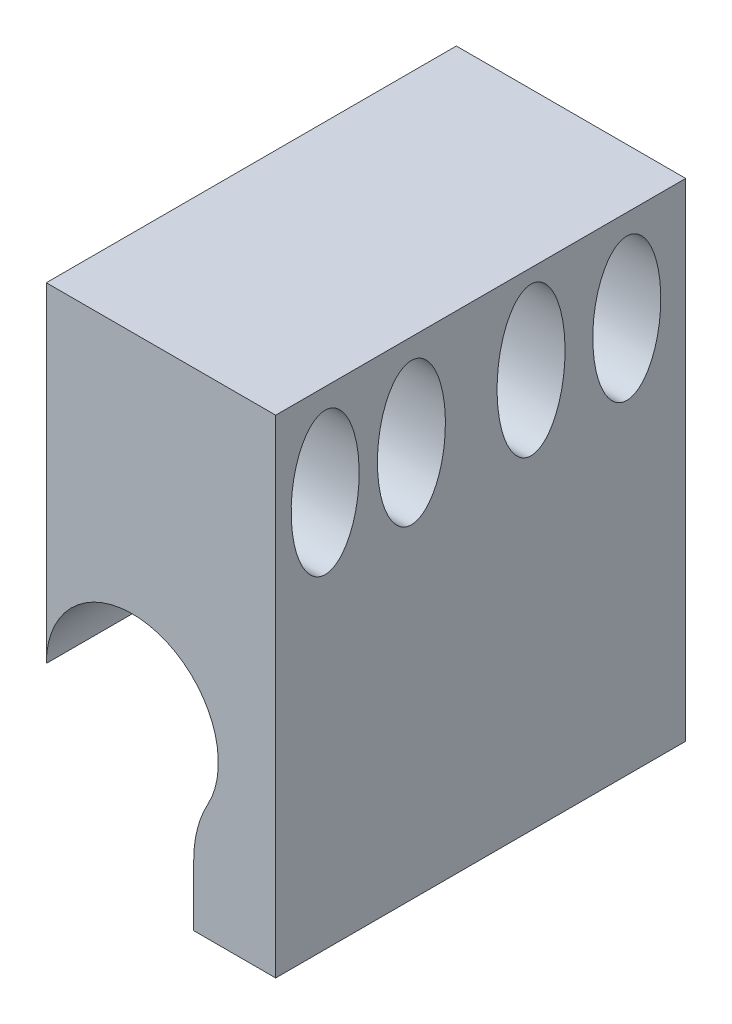
SolidWorks part; units mm, degrees
ref_plane "前视基准面" through (0, 0, 0) normal (0, 0, 1) x (1, 0, 0)
ref_plane "上视基准面" through (0, 0, 0) normal (0, 1, 0) x (1, 0, 0)
ref_plane "右视基准面" through (0, 0, 0) normal (1, 0, 0) x (0, 0, -1)
sketch "草图1" plane through (0, 0, 0) normal (0, 0, 1) x (1, 0, 0)
  line L1 (0, 0) -> (16, 0)
  line L2 (0, 0) -> (0, -34)
  line L3 (0, -34) -> (16, -34)
  line L4 (16, 0) -> (16, -34)
  dimension "D1" = 16
  dimension "D2" = 34
extrude "凸台-拉伸1" add sketch "草图1" along normal blind 28.6
sketch "草图2" plane through (0, 0, 28.6) normal (0, 0, 1) x (1, 0, 0)
  line L0 (0, 0) -> (12, 0) construction
  line L1 (16, 0) -> (0, 0) construction
  line L2 (12, 0) -> (12, -23) construction
  line L3 (12, -23) -> (6, -23) construction
  line L4 (9.3178, -34) -> (10.2842, -34)
  line L5 (0, -34) -> (16, -34) construction
  line L6 (10.2842, -34) -> (10.2842, -29.7156)
  line L7 (10.2842, -27.2007) -> (10.2842, -34)
  line L8 (0, -34) -> (0.0151, -23.4251)
  line L9 (10.2842, -34) -> (0, -34)
  arc A0 (11.2646, -25.8781) -> (0.0151, -23.4251) centre (6, -23) ccw
  arc A1 (10.2842, -29.7156) -> (11.2646, -25.8781) centre (18.2842, -29.7156) cw
  dimension "D1" = 8
extrude "切除-拉伸3" cut sketch "草图2" against normal through all both and the other way through all contours L6 A1 A0 L8 L9
sketch "草图5" plane through (0, 0, 0) normal (-1, 0, 0) x (0, 0, 1)
  line L0 (0, -34) -> (0, 0) construction
  line L1 (28.6, -23) -> (0, -23)
  line L2 (28.6, -23) -> (28.6, -34)
  line L3 (28.6, -34) -> (0, -34)
  line L4 (0, -23) -> (0, -34)
  line L5 (28.6, -34) -> (0, -34) construction
extrude "切除-拉伸4" cut sketch "草图5" against normal blind 2
sketch "草图7" plane through (0, 0, 0) normal (0, 0, -1) x (-1, 0, 0)
  line L0 (0, 0) -> (0, -23)
sketch "草图9" plane through (0, 0, 0) normal (-1, 0, 0) x (0, 0, 1)
  line L2 (28.6, 0) -> (28.6, -23) construction
  line L3 (28.6, -14.6939) -> (28.6, 0) construction
  ellipse E0 centre (4.1092, -6.3919) end of major axis (4.1092, -11.3555) minor radius 2.372
  ellipse E1 centre (10.7859, -6.1722) end of major axis (10.7859, -0.989) minor radius 2.372
  ellipse E2 centre (19.1319, -6.3919) end of major axis (19.1319, -11.3555) minor radius 2.372
  ellipse E3 centre (25.1497, -6.3919) end of major axis (25.1497, -11.3555) minor radius 2.372
  point P17 (12.7187, -6.3919)
  point P18 (12.7187, -11.3555)
  point P25 (16.7159, -9.3788)
  point P26 (16.2767, -13.7714)
  point P27 (17.3748, -3.7124)
  point P28 (17.8141, -2.7021)
  point P29 (19.1319, -6.3919)
  point P30 (19.1319, -11.3555)
  point P37 (25.1497, -6.3919)
  point P38 (25.1497, -11.3555)
  point P39 (4.1092, -6.3919)
  point P40 (4.1092, -11.3555)
  point P41 (0, 0)
  point P42 (11.357, -6.3919)
  point P43 (10.7859, -11.3555)
  point P44 (0, 0)
  point P45 (0, 0)
extrude "切除-拉伸5" cut sketch "草图9" against normal through all both and the other way through all contours E0
extrude "切除-拉伸6" cut sketch "草图9<3>" against normal through all both and the other way through all
sketch "草图9<3>" plane through (0, 0, 0) normal (-1, 0, 0) x (0, 0, 1) same geometry as "草图9"
